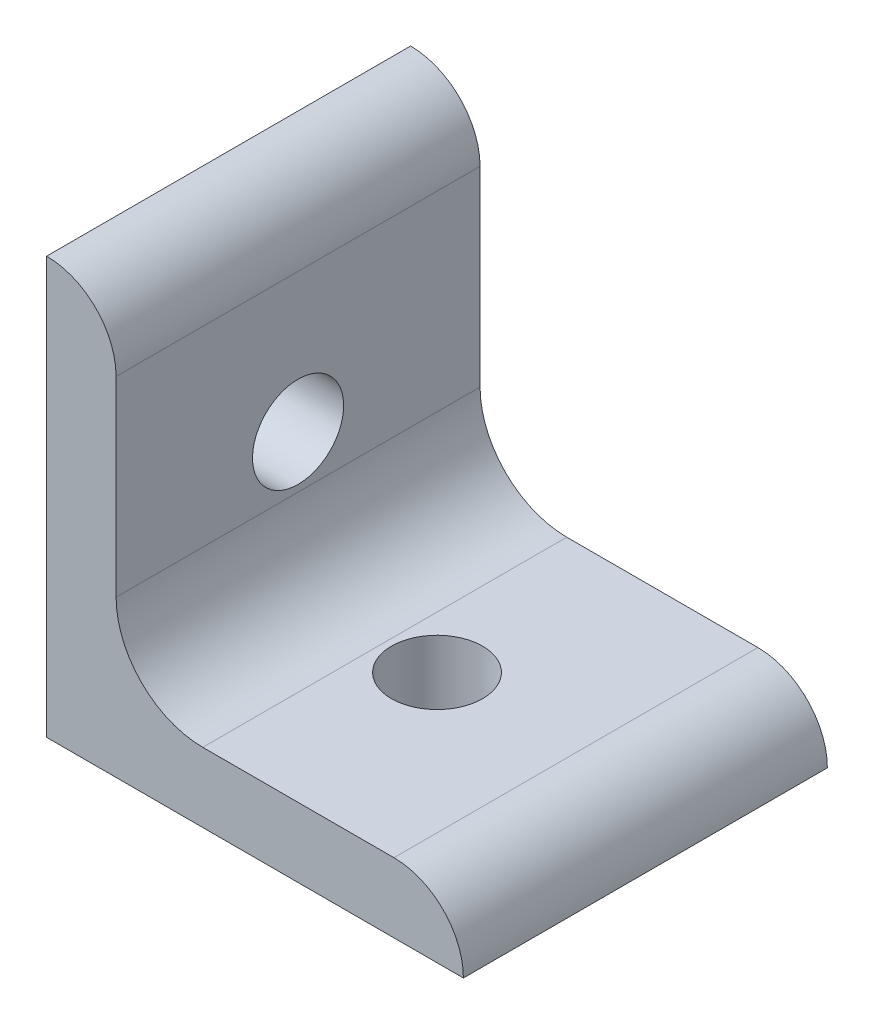
SolidWorks part; units mm, degrees
material "6105-T5 Aluminum"
ref_plane "Front Plane" through (0, 0, 0) normal (0, 0, 1) x (1, 0, 0)
ref_plane "Top Plane" through (0, 0, 0) normal (0, 1, 0) x (1, 0, 0)
ref_plane "Right Plane" through (0, 0, 0) normal (1, 0, 0) x (0, 0, -1)
sketch "Sketch2" plane through (0, 0, 0) normal (0, 0, 1) x (1, 0, 0)
  line L0 (0, 0) -> (0, 38.1)
  line L1 (38.1, 6.35) -> (38.1, 0)
  line L2 (6.35, 38.1) -> (6.35, 14.2748)
  line L3 (14.2748, 6.35) -> (38.1, 6.35)
  line L4 (0, 38.1) -> (6.35, 38.1)
  line L5 (38.1, 0) -> (0, 0)
  arc A2 (6.35, 14.2748) -> (14.2748, 6.35) centre (14.2748, 14.2748) ccw
  dimension "D3" = 38.1
  dimension "D4" = 7.9248
  dimension "D1" = 6.35
  dimension "D2" = 6.35
  dimension "D5" = 38.1
extrude "Boss-Extrude1" add sketch "Sketch2" along normal mid plane 33.274
fillet "Fillet1" radius 6.35 2 edges at (38.1, 6.35, 0) (6.35, 38.1, 0)
sketch "Sketch4" plane through (0, 0, 0) normal (0, -1, 0) x (1, 0, 0)
  line L2 (19.05, 0) -> (0, 0) construction
  line L3 (0, 16.637) -> (0, -16.637) construction
  circle A0 centre (19.05, 0) radius 4.1656
  dimension "D1" = 8.3312
  dimension "D2" = 19.05
extrude "Cut-Extrude1" cut sketch "Sketch4" against normal up to next
sketch "Sketch5" plane through (0, 0, 0) normal (-1, 0, 0) x (0, 0, 1)
  line L2 (16.637, 0) -> (-16.637, 0) construction
  line L3 (0, 19.05) -> (0, 0) construction
  circle A0 centre (0, 19.05) radius 4.1656
  dimension "D1" = 8.3312
  dimension "D2" = 19.05
extrude "Cut-Extrude2" cut sketch "Sketch5" against normal up to next
